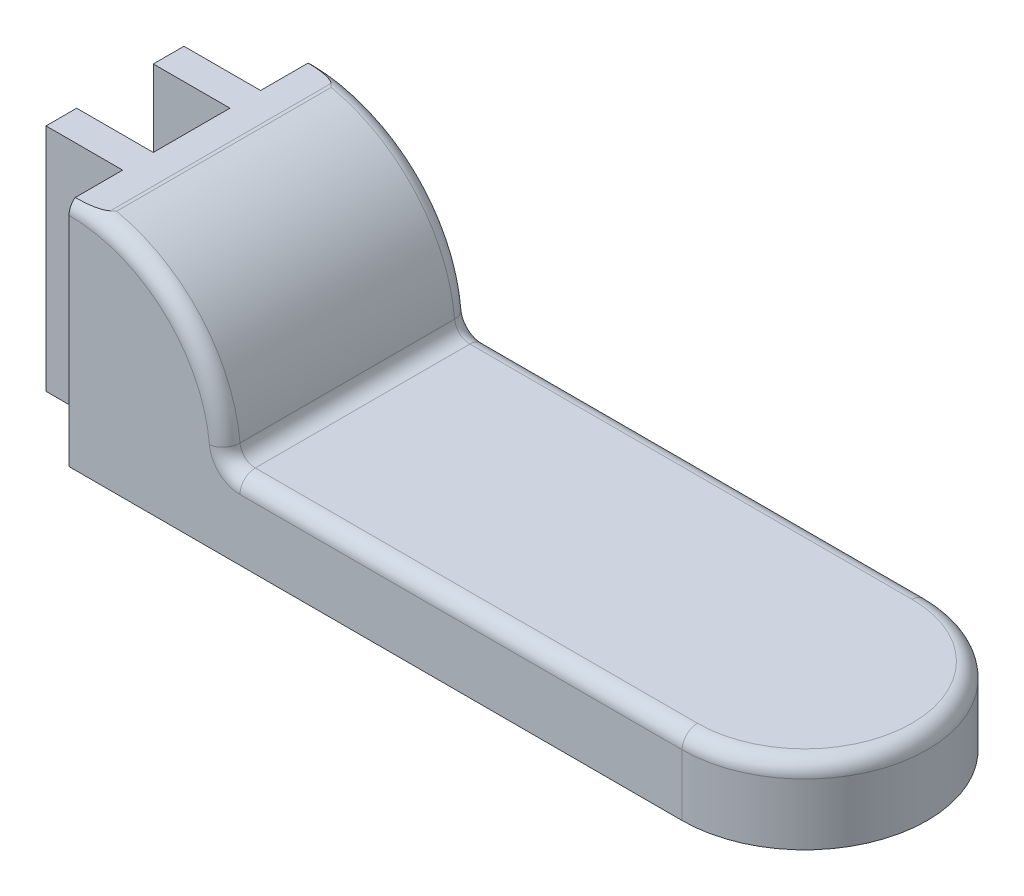
SolidWorks part; units mm, degrees
material "ABS"
ref_plane "Alzado" through (0, 0, 0) normal (0, 0, 1) x (1, 0, 0)
ref_plane "Planta" through (0, 0, 0) normal (0, 1, 0) x (1, 0, 0)
ref_plane "Vista lateral" through (0, 0, 0) normal (1, 0, 0) x (0, 0, -1)
sketch "Croquis1" plane through (0, 0, 0) normal (0, 1, 0) x (1, 0, 0)
  line L0 (0, -80) -> (-400, -80)
  line L1 (-400, -80) -> (-400, 80)
  line L2 (-400, 80) -> (0, 80)
  circle A0 centre (0, 0) radius 80
  dimension "D1" = 160
  dimension "D2" = 400
extrude "Saliente-Extruir1" add sketch "Croquis1" against normal blind 50 contours A0 | A0 L2 L1 L0
sketch "Croquis2" plane through (0, 0, 80) normal (0, 0, 1) x (1, 0, 0)
  line L0 (-400, 0) -> (-400, 100)
  line L1 (-400, 100) -> (-380, 100)
  line L2 (0, 0) -> (-400, 0) construction
  line L3 (-298.0196, 0) -> (-400, 0)
  arc A0 (-380, 100) -> (-298.0196, 0) centre (-400, 0) cw
  dimension "D1" = 100
  dimension "D2" = 20
extrude "Saliente-Extruir2" add sketch "Croquis2" against normal up to surface (160 mm away) up to face at (-200, -25, -80)
fillet "Redondeo1" radius 10 7 edges at (80, 0, 0) (-380, 100, 0)
sketch "Croquis3" plane through (-400, 0, 0) normal (-1, 0, 0) x (0, 0, 1)
  line L0 (0, -50) -> (0, 100) construction
  line L1 (80, -50) -> (-80, -50) construction
  line L2 (-75.9738, 100) -> (75.9738, 100) construction
  line L3 (45, -50) -> (25, -50)
  line L4 (-45, 100) -> (-25, 100)
  line L5 (-45, 100) -> (-45, -50)
  line L6 (-45, -50) -> (-25, -50)
  line L7 (-25, 100) -> (-25, -50)
  line L8 (45, 100) -> (25, 100)
  line L9 (45, 100) -> (45, -50)
  line L10 (25, 100) -> (25, -50)
  dimension "D1" = 25
  dimension "D2" = 20
extrude "Saliente-Extruir3" add sketch "Croquis3" along normal blind 50
sketch "Croquis4" plane through (0, -50, 0) normal (0, -1, 0) x (1, 0, 0)
  circle A0 centre (0, 0) radius 60
  dimension "D1" = 120
extrude "Cortar-Extruir1" cut sketch "Croquis4" against normal blind 30
fillet "Redondeo2" radius 3 1 edges at (0, -50, -60)
